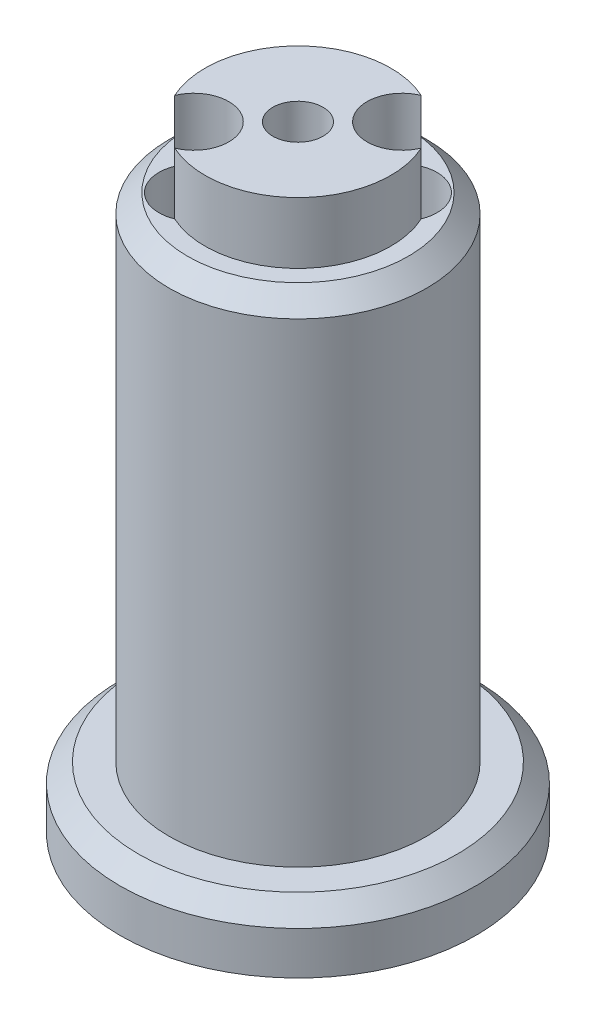
SolidWorks part; units mm, degrees
material "3DP Resin"
ref_plane "Front Plane" through (0, 0, 0) normal (0, 0, 1) x (1, 0, 0)
ref_plane "Top Plane" through (0, 0, 0) normal (0, 1, 0) x (1, 0, 0)
ref_plane "Right Plane" through (0, 0, 0) normal (1, 0, 0) x (0, 0, -1)
sketch "Sketch1" plane through (0, 0, 0) normal (0, 1, 0) x (1, 0, 0)
  circle A0 centre (0, 0) radius 14.5
  dimension "D1" = 29
extrude "Boss-Extrude1" add sketch "Sketch1" along normal blind 5
sketch "Sketch2" plane through (0, 0, 0) normal (0, -1, 0) x (1, 0, 0)
  circle A0 centre (0, 0) radius 13.05
  dimension "D1" = 26.1
extrude "Cut-Extrude1" cut sketch "Sketch2" against normal blind 3
sketch "Sketch6" plane through (0, 5, 0) normal (0, 1, 0) x (1, 0, 0)
  circle A0 centre (0, 0) radius 10.5
  dimension "D1" = 21
extrude "Pin and Motor recesses" add sketch "Sketch6" along normal blind 45.2
sketch "Sketch3" plane through (0, 5, 0) normal (0, 1, 0) x (1, 0, 0)
  line L0 (14.5, 0) -> (-14.5, 0) construction
  line L1 (0, -14.5) -> (0, 14.5) construction
  line L2 (-4.2426, 4.2426) -> (0, 0) construction
  circle A0 centre (0, 0) radius 3.1
  circle A1 centre (0, 0) radius 14.5 construction
  circle A2 centre (0, 0) radius 6 construction
  circle A3 centre (-4.2426, 4.2426) radius 1.55
  circle A5 centre (4.2426, 4.2426) radius 1.55
  circle A6 centre (4.2426, -4.2426) radius 1.55
  circle A7 centre (-4.2426, -4.2426) radius 1.55
  point P7 (0, 0)
  point P11 (0, 0)
  point P23 (0, 0)
  dimension "D1" = 6.2
  dimension "D2" = 12
  dimension "D3" = 3.1
  dimension "D4" = 45
  dimension "D5" = 4
extrude "Cut-Extrude2" cut sketch "Sketch3" along normal blind 5 from surface starting at face at (0, 3, -13.05)
sketch "Sketch7" plane through (0, 50.2, 0) normal (0, 1, 0) x (1, 0, 0)
  circle A0 centre (0, 0) radius 10.5
  circle A1 centre (0, 0) radius 7.575
  dimension "D1" = 15.15
  dimension "D2" = 21
extrude "Bearing Support" cut sketch "Sketch7" against normal blind 5
sketch "Sketch8" plane through (0, 3, 0) normal (0, -1, 0) x (1, 0, 0)
  line L0 (-13.05, 0) -> (13.05, 0) construction
  line L1 (0, -13.05) -> (0, 13.05) construction
  line L2 (-4.2426, 4.2426) -> (0, 0) construction
  line L3 (0, 0) -> (4.2426, -4.2426) construction
  circle A0 centre (0, 0) radius 2.05
  circle A1 centre (0, 0) radius 13.05 construction
  circle A2 centre (0, 0) radius 13.05 construction
  circle A3 centre (-4.2426, 4.2426) radius 1.55
  circle A4 centre (0, 0) radius 6 construction
  circle A5 centre (4.2426, -4.2426) radius 1.55
  circle A6 centre (-4.2426, 4.2426) radius 1.55 construction
  point P6 (0, 0)
  point P31 (0, 0)
  dimension "D1" = 4.1
  dimension "D2" = 3.1
  dimension "D3" = 12
  dimension "D4" = 45
extrude "M4 Hole Bore" cut sketch "Sketch8" against normal through all
sketch "Sketch9" plane through (0, 50.2, 0) normal (0, 1, 0) x (1, 0, 0)
  circle A0 centre (4.2426, 4.2426) radius 1.55 construction
  circle A1 centre (-4.2426, -4.2426) radius 1.55 construction
  circle A2 centre (4.2426, 4.2426) radius 1.55 construction
  circle A3 centre (-4.2426, -4.2426) radius 1.55 construction
  circle A4 centre (4.2426, 4.2426) radius 2.85
  circle A5 centre (-4.2426, -4.2426) radius 2.85
  dimension "D1" = 5.7
extrude "M3 Bolt Recesses" cut sketch "Sketch9" against normal blind 11
chamfer "Chamfer1" distance 1.5 angle 45 2 edges at (0, 45.2, 10.5) (0, 5, 14.5)
